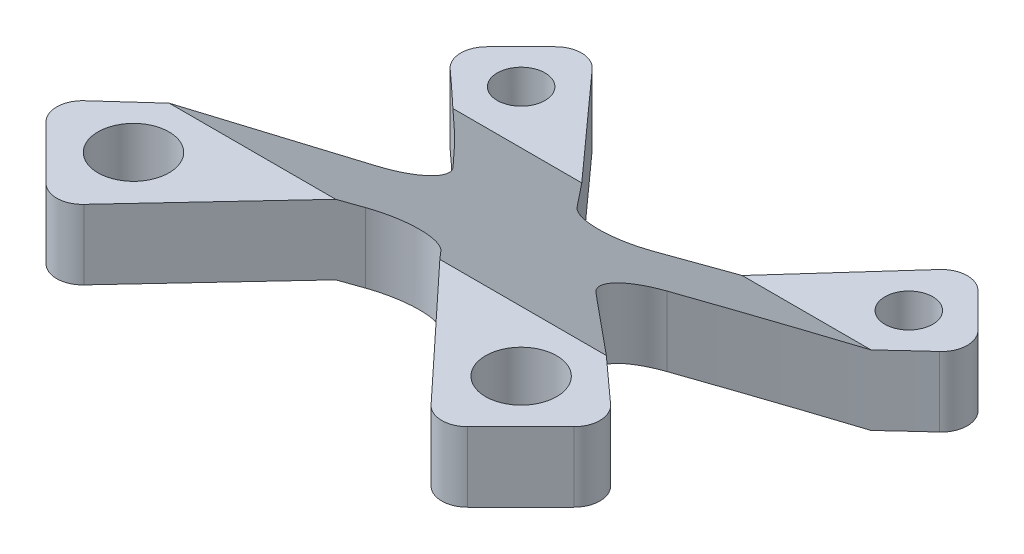
SolidWorks part; units mm, degrees
ref_plane "Front Plane" through (0, 0, 0) normal (0, 0, 1) x (1, 0, 0)
ref_plane "Top Plane" through (0, 0, 0) normal (0, 1, 0) x (1, 0, 0)
ref_plane "Right Plane" through (0, 0, 0) normal (1, 0, 0) x (0, 0, -1)
sketch "Sketch1" plane through (0, 0, 0) normal (0, 1, 0) x (1, 0, 0)
  line L0 (0, 0) -> (-8.8388, 8.8388) construction
  line L1 (-7.5, 7.5) -> (7.5, 7.5) construction
  line L2 (-7.5, 7.5) -> (-7.5, -7.5) construction
  line L3 (-7.5, -7.5) -> (7.5, -7.5) construction
  line L4 (7.5, 7.5) -> (7.5, -7.5) construction
  line L5 (-7.5, 7.5) -> (7.5, -7.5) construction
  line L6 (-7.5, -7.5) -> (7.5, 7.5) construction
  line L7 (-7.4246, 10.253) -> (-10.253, 7.4246)
  line L8 (0, 0) -> (-2.75, 0) construction
  line L9 (0, 0) -> (0, 2)
  line L10 (0, 0) -> (0, -3)
  line L11 (0, 0) -> (-9.1924, -9.1924) construction
  line L12 (-10.9602, -7.4246) -> (-7.4246, -10.9602)
  line L13 (-10.9602, -7.4246) -> (-2.75, 0)
  line L14 (-7.4246, 10.253) -> (0, 2)
  line L15 (-7.4246, -10.9602) -> (0, -3)
  circle A0 centre (-7.5, 7.5) radius 0.925
  circle A1 centre (7.5, 7.5) radius 0.925
  circle A2 centre (7.5, -7.5) radius 1.375
  circle A3 centre (-7.5, -7.5) radius 1.375
  arc A4 (-2.75, 0) -> (-10.253, 7.4246) centre (-73.3765, -63.8691) ccw
  point P0 (0, 0)
  point P15 (-8.8388, 8.8388)
  point P21 (-9.1924, -9.1924)
  dimension "D3" = 1.85
  dimension "D4" = 2.75
  dimension "D1" = 15
  dimension "D2" = 15
  dimension "D5" = 12.5
  dimension "D6" = 2
  dimension "D7" = 3
  dimension "D8" = 2.75
  dimension "D9" = 13
  dimension "D10" = 4
  dimension "D11" = 5
extrude "Boss-Extrude1" add sketch "Sketch1" along normal blind 4 and the other way blind 4 contours A4 L13 L12 L15 L10 L9 L14 L7 A3 A0 region at (-3.8898, 0, -5.9668)
ref_plane "Plane1" through (-15, 0, 0) normal (1, 0, 0) x (0, 0, -1)
mirror "Mirror2" about plane through (0, -4, 0) normal (-1, 0, 0) of bodies 101
sketch "Sketch3" plane through (-15, 0, 0) normal (1, 0, 0) x (0, 0, -1)
  line L0 (0, 0) -> (0, -4) construction
  line L1 (0, -4) -> (10.25, -4) construction
  line L2 (0, -4) -> (-10.96, -4) construction
  line L3 (10.25, -4) -> (10.25, -1.3)
  line L4 (10.25, -1.3) -> (5.45, -1.3)
  line L5 (-10.96, -4) -> (-10.96, 4) construction
  line L6 (-10.96, 4) -> (-5.16, 4)
  line L7 (5.45, -1.3) -> (-5.16, 4)
  line L8 (-10.96, 4) -> (-10.96, 1.3)
  line L9 (-10.96, 1.3) -> (-5.16, 1.3)
  line L10 (-5.16, 1.3) -> (5.45, -4)
  line L11 (5.45, -4) -> (10.25, -4)
  line L13 (10.25, -4) -> (-10.96, -4)
  line L14 (10.25, -4) -> (10.25, 4)
  line L15 (10.25, 4) -> (-10.96, 4)
  line L16 (-10.96, -4) -> (-10.96, 4)
  dimension "D1" = 4
  dimension "D2" = 10.25
  dimension "D3" = 10.96
  dimension "D4" = 2.7
  dimension "D5" = 4.8
  dimension "D6" = 8
  dimension "D7" = 5.8
  dimension "D8" = 2.7
extrude "Cut-Extrude1" cut sketch "Sketch3" against normal through all and the other way through all contours L14 L15 L7 L4 | L16 L13 L10 L9 region at (-15, 1.8137, -4.7333) region at (-15, -1.772, 4.9851)
fillet "Fillet1" radius 2 4 edges at (2.75, 0.0724, 0) (-2.75, 0.0724, 0) (0, -0.9266, -2) (0, 1.571, 3)
fillet "Fillet2" radius 1 8 edges at (-7.4246, 0, -10.253) (-10.253, -2.65, -7.4246) (7.4246, 0, -10.253) (10.253, -2.65, -7.4246) (10.9602, 2.65, 7.4246) (7.4246, 0, 10.9602) (-10.9602, 2.65, 7.4246) (-7.4246, 0, 10.9602)
